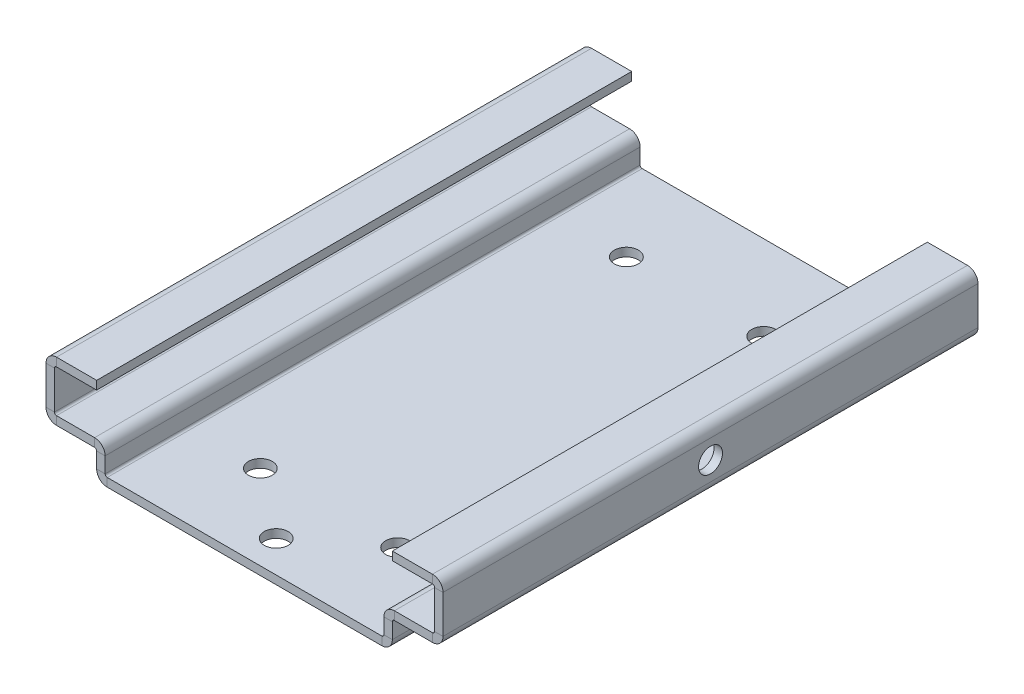
SolidWorks part; units mm, degrees
note: The reader was unsure of these and kept them because the rebuilt part matched: flange length of "Edge-Flange1", "Edge-Flange8", "Edge-Flange9", "Edge-Flange10".
ref_plane "Front Plane" through (0, 0, 0) normal (0, 0, 1) x (1, 0, 0)
ref_plane "Top Plane" through (0, 0, 0) normal (0, 1, 0) x (1, 0, 0)
ref_plane "Right Plane" through (0, 0, 0) normal (1, 0, 0) x (0, 0, -1)
sketch "Sketch1" plane through (0, 0, 0) normal (0, 1, 0) x (1, 0, 0)
  line L1 (52.5, -95) -> (-52.5, -95)
  line L2 (52.5, -95) -> (52.5, 95)
  line L3 (52.5, 95) -> (-52.5, 95)
  line L4 (-52.5, -95) -> (-52.5, 95)
  line L5 (52.5, -95) -> (-52.5, 95) construction
  line L6 (52.5, 95) -> (-52.5, -95) construction
  point P0 (0, 0)
  dimension "D1" = 190
  dimension "D2" = 105
base flange "Base-Flange1" sketch "Sketch1" thickness 3 reverse thickness direction no parameters "D1"=0.7366
edge flange "Edge-Flange1" sketch "Sketch12" flange profiles "Sketch12", "Sketch13" flange angle 90 flange length 7 flange position material inside bend radius 0.7366 thickness 3 relief rectangular parameters "D6"=10, "D8"=1
sketch "Sketch12" plane through (52.5, 0, 0) normal (1, 0, 0) x (0, 0, -1)
  line L2 (-95, 0) -> (-95, 7)
  line L3 (-95, 7) -> (95, 7)
  line L4 (95, 7) -> (95, 0)
  line L11 (-95, 0) -> (95, 0) construction
  line L12 (-95, 0) -> (95, 0)
sketch "Sketch13" plane through (-52.5, 0, 0) normal (-1, 0, 0) x (0, 0, 1)
  line L0 (-95, 0) -> (95, 0) construction
  line L1 (-95, 0) -> (95, 0)
  line L2 (-95, 0) -> (-95, 7)
  line L3 (-95, 7) -> (95, 7)
  line L4 (95, 7) -> (95, 0)
bend "EdgeBend1" bend radius 0.7366 bend angle 90 parameters "D5"=1
bend "EdgeBend2" bend radius 0.7366 bend angle 90 parameters "D5"=2
sketch "Sketch33" plane through (0, 0, 0) normal (0, 1, 0) x (1, 0, 0)
  line L2 (-48.7634, -95) -> (48.7634, -95) construction
  line L3 (48.7634, -95) -> (24.3834, -95)
  line L4 (-48.7634, -95) -> (-24.3834, -95)
  line L5 (-48.7634, -95) -> (-48.7634, 95) construction
  circle A0 centre (-24.3834, 65) radius 4.25
  circle A1 centre (24.3834, 65) radius 4.25
  circle A2 centre (-24.3834, -65) radius 4.25
  circle A3 centre (24.3834, -65) radius 4.25
extrude "Cut-Extrude1" cut sketch "Sketch33" against normal blind 10 contours A3 | A1 | A0 | A2 normal cut yes
edge flange "Edge-Flange8" sketch "Sketch58" flange profiles "Sketch58", "Sketch59" flange angle 90 flange length 15 flange position material outside bend radius 0.7366 thickness 3 relief rectangular parameters "D6"=10, "D8"=1
sketch "Sketch58" plane through (-52.5, 7, 0) normal (0, 1, 0) x (0, 0, -1)
  line L0 (-95, 0) -> (95, 0) construction
  line L1 (-95, 0) -> (95, 0)
  line L2 (-95, 0) -> (-95, 15)
  line L3 (-95, 15) -> (95, 15)
  line L4 (95, 15) -> (95, 0)
sketch "Sketch59" plane through (52.5, 7, 0) normal (0, 1, 0) x (0, 0, 1)
  line L0 (-95, 0) -> (95, 0) construction
  line L1 (-95, 0) -> (95, 0)
  line L2 (-95, 0) -> (-95, 15)
  line L3 (-95, 15) -> (95, 15)
  line L4 (95, 15) -> (95, 0)
bend "EdgeBend15" bend radius 0.7366 bend angle 90 parameters "D5"=3
bend "EdgeBend16" bend radius 0.7366 bend angle 90 parameters "D5"=4
edge flange "Edge-Flange9" sketch "Sketch64" flange profiles "Sketch64", "Sketch65" flange angle 90 flange length 15 flange position material outside bend radius 0.7366 thickness 3 relief rectangular parameters "D6"=10, "D8"=1
sketch "Sketch64" plane through (-67.5, 10, 0) normal (-1, 0, 0) x (0, 0, 1)
  line L0 (-95, 0) -> (95, 0) construction
  line L1 (-95, 0) -> (95, 0)
  line L2 (-95, 0) -> (-95, 15)
  line L3 (-95, 15) -> (95, 15)
  line L4 (95, 15) -> (95, 0)
sketch "Sketch65" plane through (67.5, 10, 0) normal (1, 0, 0) x (0, 0, -1)
  line L0 (-95, 0) -> (95, 0) construction
  line L1 (-95, 0) -> (95, 0)
  line L2 (-95, 0) -> (-95, 15)
  line L3 (-95, 15) -> (95, 15)
  line L4 (95, 15) -> (95, 0)
bend "EdgeBend17" bend radius 0.7366 bend angle 90 parameters "D5"=5
bend "EdgeBend18" bend radius 0.7366 bend angle 90 parameters "D5"=6
edge flange "Edge-Flange10" sketch "Sketch70" flange profiles "Sketch70", "Sketch71" flange angle 90 flange length 15 flange position material outside bend radius 0.7366 thickness 3 relief rectangular parameters "D6"=10, "D8"=1
sketch "Sketch70" plane through (-67.5, 25, 0) normal (0, 1, 0) x (0, 0, 1)
  line L0 (95, 0) -> (-95, 0) construction
  line L1 (95, 0) -> (-95, 0)
  line L2 (-95, 0) -> (-95, 15)
  line L3 (-95, 15) -> (95, 15)
  line L4 (95, 15) -> (95, 0)
sketch "Sketch71" plane through (67.5, 25, 0) normal (0, 1, 0) x (0, 0, -1)
  line L0 (95, 0) -> (-95, 0) construction
  line L1 (95, 0) -> (-95, 0)
  line L2 (-95, 0) -> (-95, 15)
  line L3 (-95, 15) -> (95, 15)
  line L4 (95, 15) -> (95, 0)
bend "EdgeBend19" bend radius 0.7366 bend angle 90 parameters "D5"=7
bend "EdgeBend20" bend radius 0.7366 bend angle 90 parameters "D5"=8
sketch "Sketch72" plane through (70.5, 0, 0) normal (1, 0, 0) x (0, 0, -1)
  circle A1 centre (0, 17.5) radius 4.25
extrude "Cut-Extrude4" cut sketch "Sketch72" against normal blind 10 normal cut yes
sketch "Sketch77" plane through (-70.5, 0, 0) normal (-1, 0, 0) x (0, 0, 1)
  circle A0 centre (0, 17.5) radius 4.25
extrude "Cut-Extrude5" cut sketch "Sketch77" against normal blind 10 normal cut yes
sketch "Sketch78" plane through (0, 0, 0) normal (0, 1, 0) x (1, 0, 0)
  circle A0 centre (0, -83.75) radius 4.25
extrude "Cut-Extrude8" cut sketch "Sketch78" against normal blind 10 normal cut yes
sketch "Bend-Lines1" [suppressed] plane through (0, 0, 0) normal (0, 1, 0) x (1, 0, 0)
sketch "Bounding-Box1" [suppressed] plane through (0, 0, 0) normal (0, 1, 0) x (1, 0, 0)
sheet metal parameters "Sheet-Metal4" thickness 3 parameters "D1"=0.7366
flat pattern "Flat-Pattern4" [suppressed]
sketch "Bend-Lines2" plane through (0, 0, 0) normal (0, 1, 0) x (1, 0, 0)
sketch3d "Bounding-Box2" [suppressed]
  line L0 (52.5, 95, 0) -> (52.5, -95, 0) construction
  line L1 (-52.5, 95, 0) -> (-52.5, -95, 0) construction
  line L2 (52.5, 95, 0) -> (-52.5, 95, 0) construction
  line L3 (52.5, -95, 0) -> (-52.5, -95, 0) construction
sheet metal parameters "Sheet-Metal5" thickness 3 parameters "D1"=0.7366
flat pattern "Flat-Pattern4"
sketch "Bend-Lines2" plane through (0, 0, 0) normal (0, 1, 0) x (1, 0, 0)
  line L0 (-50.52, 95) -> (-50.52, -95) construction
  line L1 (50.52, -95) -> (50.52, 95) construction
  line L2 (-50.52, 95) -> (-50.52, -95) construction
  line L3 (50.52, -95) -> (50.52, 95) construction
sketch3d "Bounding-Box2" [suppressed]
  line L0 (-58.54, 95, 0) -> (-58.54, -95, 0) construction
  line L1 (58.54, 95, 0) -> (58.54, -95, 0) construction
  line L2 (-58.54, 95, 0) -> (58.54, 95, 0) construction
  line L3 (-58.54, -95, 0) -> (58.54, -95, 0) construction
bend of the flat pattern "Flatten-<EdgeBend1>1"
bend of the flat pattern "Flatten-<EdgeBend2>1"
sheet metal parameters "Sheet-Metal9" thickness 3 parameters "D1"=0.7366
flat pattern "Flat-Pattern4"
sketch "Bend-Lines2" plane through (0, 0, 0) normal (0, 1, 0) x (1, 0, 0)
  line L0 (-50.52, 95) -> (-50.52, -95) construction
  line L1 (50.52, -95) -> (50.52, 95) construction
  line L2 (-50.52, 95) -> (-50.52, -95) construction
  line L3 (50.52, -95) -> (50.52, 95) construction
sketch3d "Bounding-Box2" [suppressed]
  line L0 (-58.54, 95, 0) -> (-58.54, -95, 0) construction
  line L1 (58.54, 95, 0) -> (58.54, -95, 0) construction
  line L2 (-58.54, 95, 0) -> (58.54, 95, 0) construction
  line L3 (-58.54, -95, 0) -> (58.54, -95, 0) construction
bend of the flat pattern "Flatten-<EdgeBend1>1"
bend of the flat pattern "Flatten-<EdgeBend2>1"
sheet metal parameters "Sheet-Metal14" thickness 3 parameters "D1"=0.7366
flat pattern "Flat-Pattern4"
sketch "Bend-Lines2" plane through (0, 0, 0) normal (0, 1, 0) x (1, 0, 0)
  line L0 (-50.52, 95) -> (-50.52, -95) construction
  line L1 (50.52, -95) -> (50.52, 95) construction
  line L2 (-50.52, 95) -> (-50.52, -95) construction
  line L3 (50.52, -95) -> (50.52, 95) construction
  line L4 (59.5601, -95) -> (59.5601, 95) construction
  line L5 (-59.5601, 95) -> (-59.5601, -95) construction
  line L6 (59.5601, -95) -> (59.5601, 95) construction
  line L7 (-59.5601, 95) -> (-59.5601, -95) construction
sketch3d "Bounding-Box2" [suppressed]
  line L0 (-75.5801, 95, 0) -> (-75.5801, -95, 0) construction
  line L1 (75.5801, 95, 0) -> (75.5801, -95, 0) construction
  line L2 (-75.5801, 95, 0) -> (75.5801, 95, 0) construction
  line L3 (-75.5801, -95, 0) -> (75.5801, -95, 0) construction
bend of the flat pattern "Flatten-<EdgeBend1>1"
bend of the flat pattern "Flatten-<EdgeBend2>1"
bend of the flat pattern "Flatten-<EdgeBend15>1"
bend of the flat pattern "Flatten-<EdgeBend16>1"
sheet metal parameters "Sheet-Metal15" thickness 3 parameters "D1"=0.7366
flat pattern "Flat-Pattern4"
sketch "Bend-Lines2" plane through (0, 0, 0) normal (0, 1, 0) x (1, 0, 0)
  line L0 (-50.52, 95) -> (-50.52, -95) construction
  line L1 (50.52, -95) -> (50.52, 95) construction
  line L2 (-50.52, 95) -> (-50.52, -95) construction
  line L3 (50.52, -95) -> (50.52, 95) construction
  line L4 (59.5601, -95) -> (59.5601, 95) construction
  line L5 (-59.5601, 95) -> (-59.5601, -95) construction
  line L6 (59.5601, -95) -> (59.5601, 95) construction
  line L7 (-59.5601, 95) -> (-59.5601, -95) construction
  line L8 (76.6001, -95) -> (76.6001, 95) construction
  line L9 (-76.6001, 95) -> (-76.6001, -95) construction
  line L10 (76.6001, -95) -> (76.6001, 95) construction
  line L11 (-76.6001, 95) -> (-76.6001, -95) construction
sketch3d "Bounding-Box2" [suppressed]
  line L0 (-92.6201, 95, 0) -> (-92.6201, -95, 0) construction
  line L1 (92.6201, 95, 0) -> (92.6201, -95, 0) construction
  line L2 (-92.6201, 95, 0) -> (92.6201, 95, 0) construction
  line L3 (-92.6201, -95, 0) -> (92.6201, -95, 0) construction
bend of the flat pattern "Flatten-<EdgeBend1>1"
bend of the flat pattern "Flatten-<EdgeBend2>1"
bend of the flat pattern "Flatten-<EdgeBend15>1"
bend of the flat pattern "Flatten-<EdgeBend16>1"
bend of the flat pattern "Flatten-<EdgeBend17>1"
bend of the flat pattern "Flatten-<EdgeBend18>1"
sheet metal parameters "Sheet-Metal16" thickness 3 parameters "D1"=0.7366
flat pattern "Flat-Pattern4" [suppressed]
sketch "Bend-Lines2" plane through (0, 0, 0) normal (0, 1, 0) x (1, 0, 0)
  line L0 (-50.52, 95) -> (-50.52, -95) construction
  line L1 (50.52, -95) -> (50.52, 95) construction
  line L2 (-50.52, 95) -> (-50.52, -95) construction
  line L3 (50.52, -95) -> (50.52, 95) construction
  line L4 (59.5601, -95) -> (59.5601, 95) construction
  line L5 (-59.5601, 95) -> (-59.5601, -95) construction
  line L6 (59.5601, -95) -> (59.5601, 95) construction
  line L7 (-59.5601, 95) -> (-59.5601, -95) construction
  line L8 (76.6001, -95) -> (76.6001, 95) construction
  line L9 (-76.6001, 95) -> (-76.6001, -95) construction
  line L10 (76.6001, -95) -> (76.6001, 95) construction
  line L11 (-76.6001, 95) -> (-76.6001, -95) construction
  line L12 (93.6402, -95) -> (93.6402, 95) construction
  line L13 (-93.6402, 95) -> (-93.6402, -95) construction
  line L14 (93.6402, -95) -> (93.6402, 95) construction
  line L15 (-93.6402, 95) -> (-93.6402, -95) construction
sketch3d "Bounding-Box2" [suppressed]
  line L0 (109.6602, -95, 0) -> (-109.6602, -95, 0) construction
  line L1 (109.6602, 95, 0) -> (-109.6602, 95, 0) construction
  line L2 (109.6602, -95, 0) -> (109.6602, 95, 0) construction
  line L3 (-109.6602, -95, 0) -> (-109.6602, 95, 0) construction
bend of the flat pattern "Flatten-<EdgeBend1>1"
bend of the flat pattern "Flatten-<EdgeBend2>1"
bend of the flat pattern "Flatten-<EdgeBend15>1"
bend of the flat pattern "Flatten-<EdgeBend16>1"
bend of the flat pattern "Flatten-<EdgeBend17>1"
bend of the flat pattern "Flatten-<EdgeBend18>1"
bend of the flat pattern "Flatten-<EdgeBend19>1"
bend of the flat pattern "Flatten-<EdgeBend20>1"
sketch "Sketch72-2" [suppressed] plane through (67.6201, -3, 0) normal (0, -1, 0) x (0, 0, -1)
  circle A0 centre (0, 17.5) radius 4.25
sketch "Sketch73-1" [suppressed] plane through (-67.6201, -3, 0) normal (0, -1, 0) x (0, 0, 1)
  circle A0 centre (0, 17.5) radius 3.9196
sheet metal parameters "Sheet-Metal19" thickness 3 parameters "D1"=0.7366
flat pattern "Flat-Pattern4" [suppressed]
sketch "Bend-Lines2" plane through (0, 0, 0) normal (0, 1, 0) x (1, 0, 0)
  line L0 (-50.52, 95) -> (-50.52, -95) construction
  line L1 (50.52, -95) -> (50.52, 95) construction
  line L2 (-50.52, 95) -> (-50.52, -95) construction
  line L3 (50.52, -95) -> (50.52, 95) construction
  line L4 (59.5601, -95) -> (59.5601, 95) construction
  line L5 (-59.5601, 95) -> (-59.5601, -95) construction
  line L6 (59.5601, -95) -> (59.5601, 95) construction
  line L7 (-59.5601, 95) -> (-59.5601, -95) construction
  line L8 (76.6001, -95) -> (76.6001, 95) construction
  line L9 (-76.6001, 95) -> (-76.6001, -95) construction
  line L10 (76.6001, -95) -> (76.6001, 95) construction
  line L11 (-76.6001, 95) -> (-76.6001, -95) construction
  line L12 (93.6402, -95) -> (93.6402, 95) construction
  line L13 (-93.6402, 95) -> (-93.6402, -95) construction
  line L14 (93.6402, -95) -> (93.6402, 95) construction
  line L15 (-93.6402, 95) -> (-93.6402, -95) construction
sketch3d "Bounding-Box2" [suppressed]
  line L0 (109.6602, -95, 0) -> (-109.6602, -95, 0) construction
  line L1 (109.6602, 95, 0) -> (-109.6602, 95, 0) construction
  line L2 (109.6602, -95, 0) -> (109.6602, 95, 0) construction
  line L3 (-109.6602, -95, 0) -> (-109.6602, 95, 0) construction
bend of the flat pattern "Flatten-<EdgeBend1>1"
bend of the flat pattern "Flatten-<EdgeBend2>1"
bend of the flat pattern "Flatten-<EdgeBend15>1"
bend of the flat pattern "Flatten-<EdgeBend16>1"
bend of the flat pattern "Flatten-<EdgeBend17>1"
bend of the flat pattern "Flatten-<EdgeBend18>1"
bend of the flat pattern "Flatten-<EdgeBend19>1"
bend of the flat pattern "Flatten-<EdgeBend20>1"
sketch "Sketch72-2" [suppressed] plane through (67.6201, -3, 0) normal (0, -1, 0) x (0, 0, -1)
  circle A1 centre (0, 17.5) radius 4.25
sheet metal parameters "Sheet-Metal20" thickness 3 parameters "D1"=0.7366
flat pattern "Flat-Pattern4" [suppressed]
sketch "Bend-Lines2" plane through (0, 0, 0) normal (0, 1, 0) x (1, 0, 0)
  line L0 (-50.52, 95) -> (-50.52, -95) construction
  line L1 (50.52, -95) -> (50.52, 95) construction
  line L2 (-50.52, 95) -> (-50.52, -95) construction
  line L3 (50.52, -95) -> (50.52, 95) construction
  line L4 (59.5601, -95) -> (59.5601, 95) construction
  line L5 (-59.5601, 95) -> (-59.5601, -95) construction
  line L6 (59.5601, -95) -> (59.5601, 95) construction
  line L7 (-59.5601, 95) -> (-59.5601, -95) construction
  line L8 (76.6001, -95) -> (76.6001, 95) construction
  line L9 (-76.6001, 95) -> (-76.6001, -95) construction
  line L10 (76.6001, -95) -> (76.6001, 95) construction
  line L11 (-76.6001, 95) -> (-76.6001, -95) construction
  line L12 (93.6402, -95) -> (93.6402, 95) construction
  line L13 (-93.6402, 95) -> (-93.6402, -95) construction
  line L14 (93.6402, -95) -> (93.6402, 95) construction
  line L15 (-93.6402, 95) -> (-93.6402, -95) construction
sketch3d "Bounding-Box2" [suppressed]
  line L0 (109.6602, -95, 0) -> (-109.6602, -95, 0) construction
  line L1 (109.6602, 95, 0) -> (-109.6602, 95, 0) construction
  line L2 (109.6602, -95, 0) -> (109.6602, 95, 0) construction
  line L3 (-109.6602, -95, 0) -> (-109.6602, 95, 0) construction
bend of the flat pattern "Flatten-<EdgeBend1>1"
bend of the flat pattern "Flatten-<EdgeBend2>1"
bend of the flat pattern "Flatten-<EdgeBend15>1"
bend of the flat pattern "Flatten-<EdgeBend16>1"
bend of the flat pattern "Flatten-<EdgeBend17>1"
bend of the flat pattern "Flatten-<EdgeBend18>1"
bend of the flat pattern "Flatten-<EdgeBend19>1"
bend of the flat pattern "Flatten-<EdgeBend20>1"
sketch "Sketch72-2" [suppressed] plane through (67.6201, -3, 0) normal (0, -1, 0) x (0, 0, -1)
  circle A1 centre (0, 17.5) radius 4.25
sheet metal parameters "Sheet-Metal23" thickness 3 parameters "D1"=0.7366
flat pattern "Flat-Pattern4" [suppressed]
sketch "Bend-Lines2" plane through (0, 0, 0) normal (0, 1, 0) x (1, 0, 0)
  line L0 (-50.52, 95) -> (-50.52, -95) construction
  line L1 (50.52, -95) -> (50.52, 95) construction
  line L2 (-50.52, 95) -> (-50.52, -95) construction
  line L3 (50.52, -95) -> (50.52, 95) construction
  line L4 (59.5601, -95) -> (59.5601, 95) construction
  line L5 (-59.5601, 95) -> (-59.5601, -95) construction
  line L6 (59.5601, -95) -> (59.5601, 95) construction
  line L7 (-59.5601, 95) -> (-59.5601, -95) construction
  line L8 (76.6001, -95) -> (76.6001, 95) construction
  line L9 (-76.6001, 95) -> (-76.6001, -95) construction
  line L10 (76.6001, -95) -> (76.6001, 95) construction
  line L11 (-76.6001, 95) -> (-76.6001, -95) construction
  line L12 (93.6402, -95) -> (93.6402, 95) construction
  line L13 (-93.6402, 95) -> (-93.6402, -95) construction
  line L14 (93.6402, -95) -> (93.6402, 95) construction
  line L15 (-93.6402, 95) -> (-93.6402, -95) construction
sketch3d "Bounding-Box2" [suppressed]
  line L0 (109.6602, -95, 0) -> (-109.6602, -95, 0) construction
  line L1 (109.6602, 95, 0) -> (-109.6602, 95, 0) construction
  line L2 (109.6602, -95, 0) -> (109.6602, 95, 0) construction
  line L3 (-109.6602, -95, 0) -> (-109.6602, 95, 0) construction
bend of the flat pattern "Flatten-<EdgeBend1>1"
bend of the flat pattern "Flatten-<EdgeBend2>1"
bend of the flat pattern "Flatten-<EdgeBend15>1"
bend of the flat pattern "Flatten-<EdgeBend16>1"
bend of the flat pattern "Flatten-<EdgeBend17>1"
bend of the flat pattern "Flatten-<EdgeBend18>1"
bend of the flat pattern "Flatten-<EdgeBend19>1"
bend of the flat pattern "Flatten-<EdgeBend20>1"
sketch "Sketch72-2" [suppressed] plane through (67.6201, -3, 0) normal (0, -1, 0) x (0, 0, -1)
  circle A1 centre (0, 17.5) radius 4.25
equation "\"4.2512.7366mm\"=12.7366"
